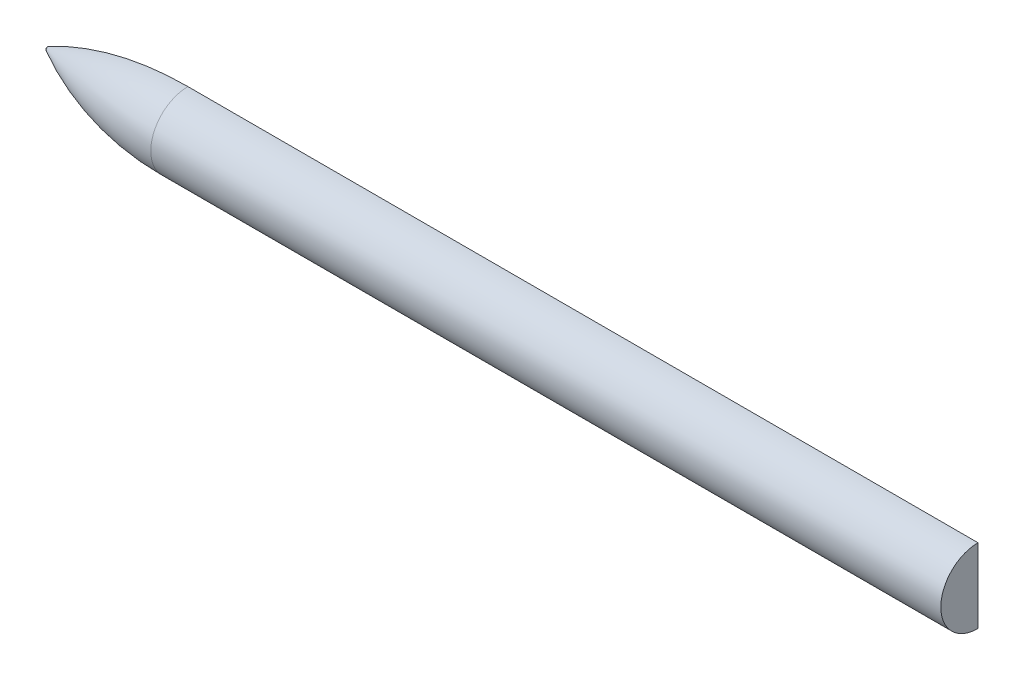
SolidWorks part; units mm, degrees
ref_plane "Front Plane" through (0, 0, 0) normal (0, 0, 1) x (1, 0, 0)
ref_plane "Top Plane" through (0, 0, 0) normal (0, 1, 0) x (1, 0, 0)
ref_plane "Right Plane" through (0, 0, 0) normal (1, 0, 0) x (0, 0, -1)
sketch "Sketch1" plane through (0, 0, 0) normal (0, 0, 1) x (1, 0, 0)
  line L0 (-668.9542, 0) -> (1072.3595, 0) construction
  line L1 (500, 0) -> (500, 40)
  line L2 (500, 40) -> (-350, 40)
  line L3 (-502, 0) -> (500, 0)
  arc A0 (-350, 40) -> (-500, 2.5) centre (-350, -278.75) ccw
  arc A1 (-500, 2.5) -> (-502, 0) centre (-498.093, -1.0756) ccw
  dimension "D1" = 80
  dimension "D2" = 150
  dimension "D3" = 1000
  dimension "D4" = 5
  dimension "D5" = 2
  dimension "D6" = 500
revolve "Revolve1" add sketch "Sketch1" angle 180 about L0
equation "\"Diameter\"=80"
equation "\"LengthCone\"=57.2246"
equation "\"LengthReference\"=1000"
equation "\"D6@Sketch1\"=\"LengthReference\"/2"
equation "\"D3@Sketch1\"=\"LengthReference\""
equation "\"D1@Sketch1\"=\"Diameter\""
